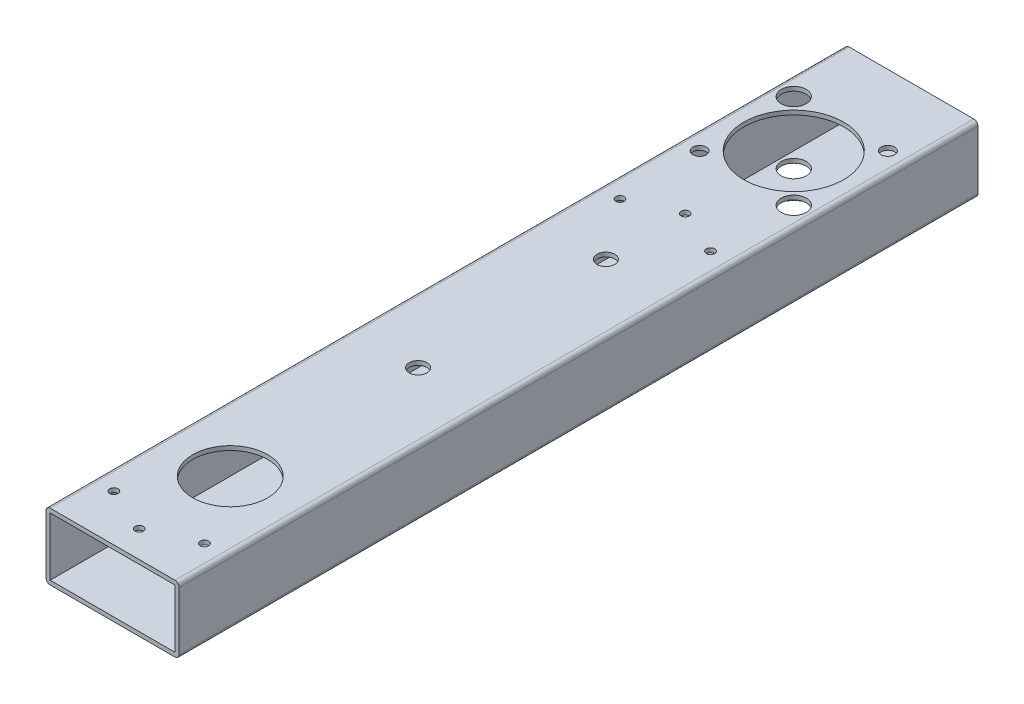
SolidWorks part; units mm, degrees
ref_plane "Front Plane" through (0, 0, 0) normal (0, 0, 1) x (1, 0, 0)
ref_plane "Top Plane" through (0, 0, 0) normal (0, 1, 0) x (1, 0, 0)
ref_plane "Right Plane" through (0, 0, 0) normal (1, 0, 0) x (0, 0, -1)
sketch "Sketch1" plane through (0, 0, 0) normal (0, 0, 1) x (1, 0, 0)
  line L0 (-23.8125, 11.1125) -> (23.8125, 11.1125)
  line L1 (-23.8125, -12.7) -> (23.8125, -12.7)
  line L2 (-25.4, -11.1125) -> (-25.4, 11.1125)
  line L3 (-23.8125, 12.7) -> (23.8125, 12.7)
  line L4 (25.4, -11.1125) -> (25.4, 11.1125)
  line L5 (-25.4, -12.7) -> (25.4, 12.7) construction
  line L6 (-25.4, 12.7) -> (25.4, -12.7) construction
  line L7 (23.8125, -11.1125) -> (23.8125, 11.1125)
  line L8 (-23.8125, -11.1125) -> (23.8125, -11.1125)
  line L9 (-23.8125, -11.1125) -> (-23.8125, 11.1125)
  line L10 (-25.4, -12.7) -> (25.4, -12.7) construction
  line L11 (-25.4, -12.7) -> (-25.4, 12.7) construction
  line L12 (25.4, -12.7) -> (25.4, 12.7) construction
  line L13 (-25.4, 12.7) -> (25.4, 12.7) construction
  arc A0 (-23.8125, -12.7) -> (-25.4, -11.1125) centre (-23.8125, -11.1125) cw
  arc A1 (23.8125, -12.7) -> (25.4, -11.1125) centre (23.8125, -11.1125) ccw
  arc A2 (23.8125, 12.7) -> (25.4, 11.1125) centre (23.8125, 11.1125) cw
  arc A3 (-25.4, 11.1125) -> (-23.8125, 12.7) centre (-23.8125, 11.1125) cw
  point P0 (0, 0)
  dimension "D4" = 1.5875
  dimension "D1" = 25.4
  dimension "D2" = 50.8
  dimension "D3" = 1.5875
extrude "Boss-Extrude1" add sketch "Sketch1" along normal blind 304.8
sketch "Sketch2" plane through (0, 12.7, 0) normal (0, 1, 0) x (1, 0, 0)
  line L0 (0, -259.9) -> (0, -304.8) construction
  line L1 (23.8125, -304.8) -> (-23.8125, -304.8) construction
  line L4 (0, -259.9) -> (0, -44.9) construction
  line L7 (0, -44.9) -> (0, 0) construction
  line L8 (23.8125, 0) -> (-23.8125, 0) construction
  circle A10 centre (0, -259.9) radius 14.2875
  circle A11 centre (0, -44.9) radius 19.05
  dimension "D1" = 38.1
  dimension "D4" = 215
  dimension "D2" = 28.575
extrude "Cut-Extrude1" cut sketch "Sketch2" against normal up to next and the other way through all
sketch "Sketch3" plane through (0, -12.7, 0) normal (0, -1, 0) x (1, 0, 0)
  circle A0 centre (0, 44.9) radius 12.7
  circle A1 centre (0, 259.9) radius 12.7
  circle A7 centre (0, 259.9) radius 14.2875 construction
  circle A8 centre (0, 44.9) radius 19.05 construction
  dimension "D1" = 25.4
  dimension "D2" = 25.4
extrude "Cut-Extrude2" cut sketch "Sketch3" against normal up to next and the other way through all
sketch "Sketch7" plane through (0, 11.1125, 0) normal (0, -1, 0) x (1, 0, 0)
  arc A16 (20.5132, 26.9395) -> (15.4078, 26.9395) centre (17.9605, 26.9395) ccw construction
  arc A17 (15.4078, 26.9395) -> (20.5132, 26.9395) centre (17.9605, 26.9395) ccw construction
  arc A18 (-15.4078, 62.8605) -> (-20.5132, 62.8605) centre (-17.9605, 62.8605) ccw construction
  arc A19 (-20.5132, 62.8605) -> (-15.4078, 62.8605) centre (-17.9605, 62.8605) ccw construction
  arc A20 (20.5132, 26.9395) -> (15.4078, 26.9395) centre (17.9605, 26.9395) ccw
  arc A21 (15.4078, 26.9395) -> (20.5132, 26.9395) centre (17.9605, 26.9395) ccw
  arc A22 (-15.4078, 62.8605) -> (-20.5132, 62.8605) centre (-17.9605, 62.8605) ccw
  arc A23 (-20.5132, 62.8605) -> (-15.4078, 62.8605) centre (-17.9605, 62.8605) ccw
  arc A32 (-15.4078, 26.9395) -> (-20.5132, 26.9395) centre (-17.9605, 26.9395) ccw construction
  arc A33 (-20.5132, 26.9395) -> (-15.4078, 26.9395) centre (-17.9605, 26.9395) ccw construction
  arc A34 (15.4078, 62.8605) -> (20.5132, 62.8605) centre (17.9605, 62.8605) ccw construction
  arc A35 (20.5132, 62.8605) -> (15.4078, 62.8605) centre (17.9605, 62.8605) ccw construction
  arc A36 (-15.4078, 26.9395) -> (-20.5132, 26.9395) centre (-17.9605, 26.9395) ccw construction
  arc A37 (-20.5132, 26.9395) -> (-15.4078, 26.9395) centre (-17.9605, 26.9395) ccw construction
  arc A38 (15.4078, 62.8605) -> (20.5132, 62.8605) centre (17.9605, 62.8605) ccw construction
  arc A39 (20.5132, 62.8605) -> (15.4078, 62.8605) centre (17.9605, 62.8605) ccw construction
  circle A40 centre (17.9605, 62.8605) radius 4.7625
  circle A41 centre (-17.9605, 26.9395) radius 4.7625
  dimension "D2" = 9.525
extrude "Cut-Extrude3" cut sketch "Sketch7" against normal through all and the other way through all
sketch "Sketch8" plane through (0, 12.7, 0) normal (0, 1, 0) x (1, 0, 0)
  line L0 (0, -44.9) -> (0, -259.9) construction
  circle A0 centre (0, -116.5667) radius 3.3782
  circle A2 centre (0, -188.2333) radius 3.3782
  dimension "D1" = 6.7564
  dimension "D2" = 71.6667
  dimension "D3" = 71.6667
extrude "Cut-Extrude4" cut sketch "Sketch8" against normal up to next and the other way through all
sketch "Sketch9" plane through (0, -12.7, 0) normal (0, -1, 0) x (1, 0, 0)
  line L0 (0, 44.9) -> (0, 259.9) construction
  circle A0 centre (0, 116.5667) radius 7.9375
  circle A2 centre (0, 116.5667) radius 3.3782 construction
  circle A4 centre (0, 188.2333) radius 7.9375
  circle A5 centre (0, 188.2333) radius 3.3782 construction
  dimension "D1" = 15.875
extrude "Cut-Extrude5" cut sketch "Sketch9" against normal up to next and the other way through all
sketch "Sketch10" plane through (0, 12.7, 0) normal (0, 1, 0) x (1, 0, 0)
  circle A0 centre (17.272, -287.02) radius 1.5875 construction
  circle A1 centre (-17.272, -287.02) radius 1.5875 construction
  circle A2 centre (0, -294.64) radius 1.5875 construction
  circle A3 centre (17.272, -93.922) radius 1.5875 construction
  circle A4 centre (0, -86.302) radius 1.5875 construction
  circle A5 centre (-17.272, -93.922) radius 1.5875 construction
  circle A6 centre (17.272, -287.02) radius 1.5875
  circle A7 centre (-17.272, -287.02) radius 1.5875
  circle A8 centre (0, -294.64) radius 1.5875
  circle A9 centre (17.272, -93.922) radius 1.5875
  circle A10 centre (0, -86.302) radius 1.5875
  circle A11 centre (-17.272, -93.922) radius 1.5875
extrude "Cut-Extrude6" cut sketch "Sketch10" against normal up to next and the other way through all
